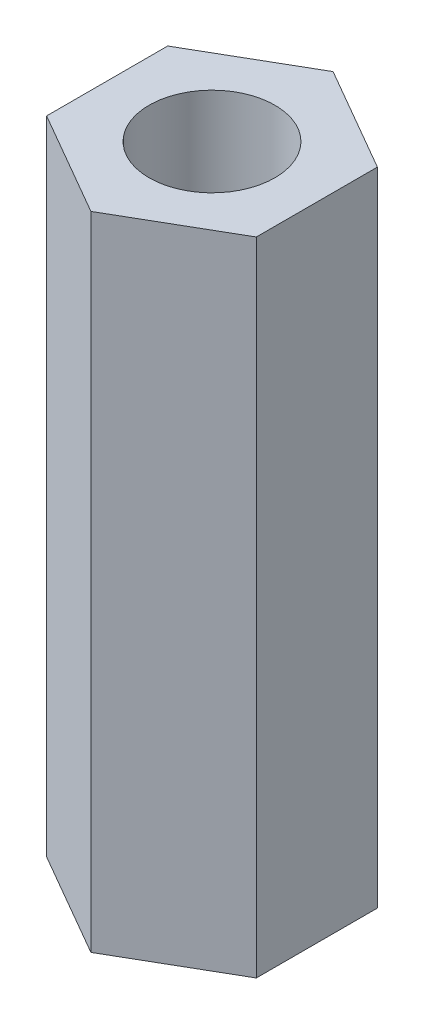
SolidWorks part; units mm, degrees
ref_plane "前基準面" through (0, 0, 0) normal (0, 0, 1) x (1, 0, 0)
ref_plane "上基準面" through (0, 0, 0) normal (0, 1, 0) x (1, 0, 0)
ref_plane "右基準面" through (0, 0, 0) normal (1, 0, 0) x (0, 0, -1)
sketch "草圖1" plane through (0, 0, 0) normal (0, 1, 0) x (1, 0, 0)
  line L0 (0, -5.1664) -> (0, 5.1664) construction
  line L1 (0, 2.8868) -> (-2.5, 1.4434)
  line L2 (-2.5, 1.4434) -> (-2.5, -1.4434)
  line L3 (-2.5, -1.4434) -> (0, -2.8868)
  line L4 (0, -2.8868) -> (2.5, -1.4434)
  line L5 (2.5, -1.4434) -> (2.5, 1.4434)
  line L6 (2.5, 1.4434) -> (0, 2.8868)
  circle A0 centre (0, 0) radius 1.5
  circle A1 centre (0, 0) radius 2.5 construction
  point P16 (0, 0)
  dimension "D1" = 3
  dimension "D2" = 5
extrude "填料-伸長1" add sketch "草圖1" along normal blind 15.3
